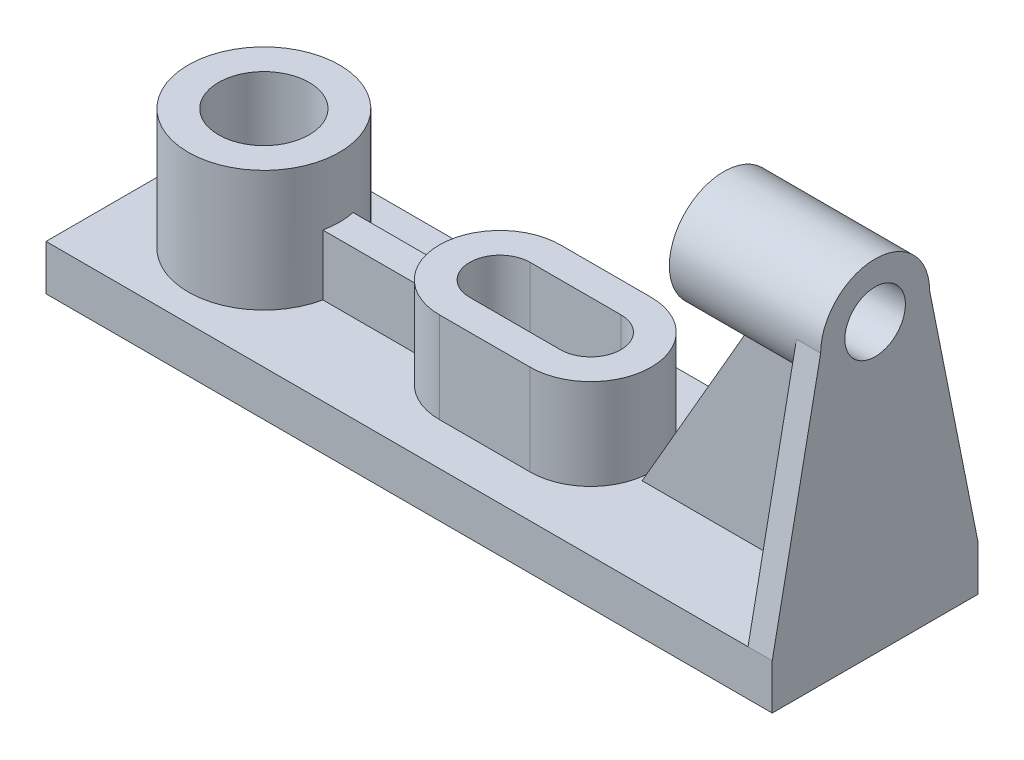
SolidWorks part; units mm, degrees
ref_plane "Front Plane" through (0, 0, 0) normal (0, 0, 1) x (1, 0, 0)
ref_plane "Top Plane" through (0, 0, 0) normal (0, 1, 0) x (1, 0, 0)
ref_plane "Right Plane" through (0, 0, 0) normal (1, 0, 0) x (0, 0, -1)
sketch "Sketch2" plane through (0, 0, 0) normal (0, 1, 0) x (1, 0, 0)
  line L1 (-120, 34) -> (120, 34)
  line L2 (-120, 34) -> (-120, -34)
  line L3 (-120, -34) -> (120, -34)
  line L4 (120, 34) -> (120, -34)
  line L5 (-120, 34) -> (120, -34) construction
  line L6 (-120, -34) -> (120, 34) construction
  point P0 (0, 0)
  dimension "D1" = 240
  dimension "D2" = 68
extrude "Boss-Extrude1" add sketch "Sketch2" along normal blind 15
sketch "Sketch4" plane through (0, 15, 0) normal (0, 1, 0) x (1, 0, 0)
  line L3 (120, -34) -> (120, 34) construction
  circle A0 centre (-82, 0) radius 25
  circle A5 centre (-82, 0) radius 15
  dimension "D3" = 50
  dimension "D7" = 30
  dimension "D1" = 202
extrude "Boss-Extrude4" add sketch "Sketch4" along normal blind 40 contours A5 | A0
sketch "Sketch7" plane through (0, 15, 0) normal (0, 1, 0) x (1, 0, 0)
  circle A0 centre (-82, 0) radius 15
extrude "Cut-Extrude2" cut sketch "Sketch7" against normal blind 40
sketch "Sketch8" plane through (0, 15, 0) normal (0, 1, 0) x (1, 0, 0)
  line L0 (-4, 0) -> (26, 0) construction
  line L1 (-4, 20) -> (26, 20)
  line L2 (-4, -20) -> (26, -20)
  line L3 (120, -34) -> (120, 34) construction
  line L4 (-4, 10) -> (26, 10)
  line L5 (-4, -10) -> (26, -10)
  arc A0 (-4, 20) -> (-4, -20) centre (-4, 0) ccw
  arc A1 (26, -20) -> (26, 20) centre (26, 0) ccw
  arc A2 (26, -10) -> (26, 10) centre (26, 0) ccw
  arc A3 (-4, 10) -> (-4, -10) centre (-4, 0) ccw
  point P4 (11, 0)
  dimension "D1" = 20
  dimension "D2" = 30
  dimension "D3" = 124
  dimension "D4" = 10
extrude "Boss-Extrude5" add sketch "Sketch8" along normal blind 30 contours L2 A1 L1 A0
sketch "Sketch9" plane through (0, 45, 0) normal (0, 1, 0) x (1, 0, 0)
  line L4 (-4, -10) -> (26, -10)
  line L5 (26, 10) -> (-4, 10)
  line L6 (-4, -10) -> (26, -10)
  line L7 (26, 10) -> (-4, 10)
  arc A4 (-4, 10) -> (-4, -10) centre (-4, 0) ccw
  arc A5 (26, -10) -> (26, 10) centre (26, 0) ccw
  arc A6 (-4, 10) -> (-4, -10) centre (-4, 0) ccw
  arc A7 (26, -10) -> (26, 10) centre (26, 0) ccw
  dimension "D1" = 10
extrude "Cut-Extrude3" cut sketch "Sketch9" against normal blind 77
sketch "Sketch11" plane through (0, 0, 0) normal (0, 0, 1) x (1, 0, 0)
  line L0 (-57, 35) -> (-24, 35)
  line L1 (-57, 15) -> (-57, 55) construction
  line L2 (-24, 45) -> (-24, 15) construction
  line L3 (-120, 15) -> (120, 15) construction
  dimension "D1" = 20
rib "Rib3" sketch "Sketch11" sketch "Sketch11" thickness 10 extrusion direction parallel to sketch draft on no parameters "D1"=10
sketch "Sketch12" plane through (120, 0, 0) normal (1, 0, 0) x (0, 0, -1)
  line L0 (0, 15) -> (0, 95) construction
  line L1 (-34, 15) -> (34, 15) construction
  line L2 (-18, 95) -> (-34, 15)
  line L3 (18, 95) -> (34, 15)
  line L4 (-34, 15) -> (34, 15)
  arc A0 (18, 95) -> (-18, 95) centre (0, 95) ccw
  dimension "D1" = 36
  dimension "D2" = 95
extrude "Boss-Extrude6" add sketch "Sketch12" against normal blind 8
sketch "Sketch13" plane through (112, 0, 0) normal (-1, 0, 0) x (0, 0, 1)
  circle A0 centre (0, 95) radius 18
extrude "Boss-Extrude7" add sketch "Sketch13" along normal blind 42
sketch "Sketch14" plane through (70, 0, 0) normal (-1, 0, 0) x (0, 0, 1)
  circle A0 centre (0, 95) radius 10
  dimension "D1" = 20
extrude "Cut-Extrude4" cut sketch "Sketch14" against normal blind 67
sketch "Sketch19" plane through (0, 0, 0) normal (0, 0, 1) x (1, 0, 0)
  line L6 (82.7957, 77) -> (47, 15)
  line L7 (70, 77) -> (112, 77) construction
  line L8 (-120, 15) -> (112, 15) construction
  dimension "D1" = 65
  dimension "D2" = 60
rib "Rib14" sketch "Sketch19" sketch "Sketch19" thickness 8 extrusion direction parallel to sketch draft on no parameters "D1"=8
